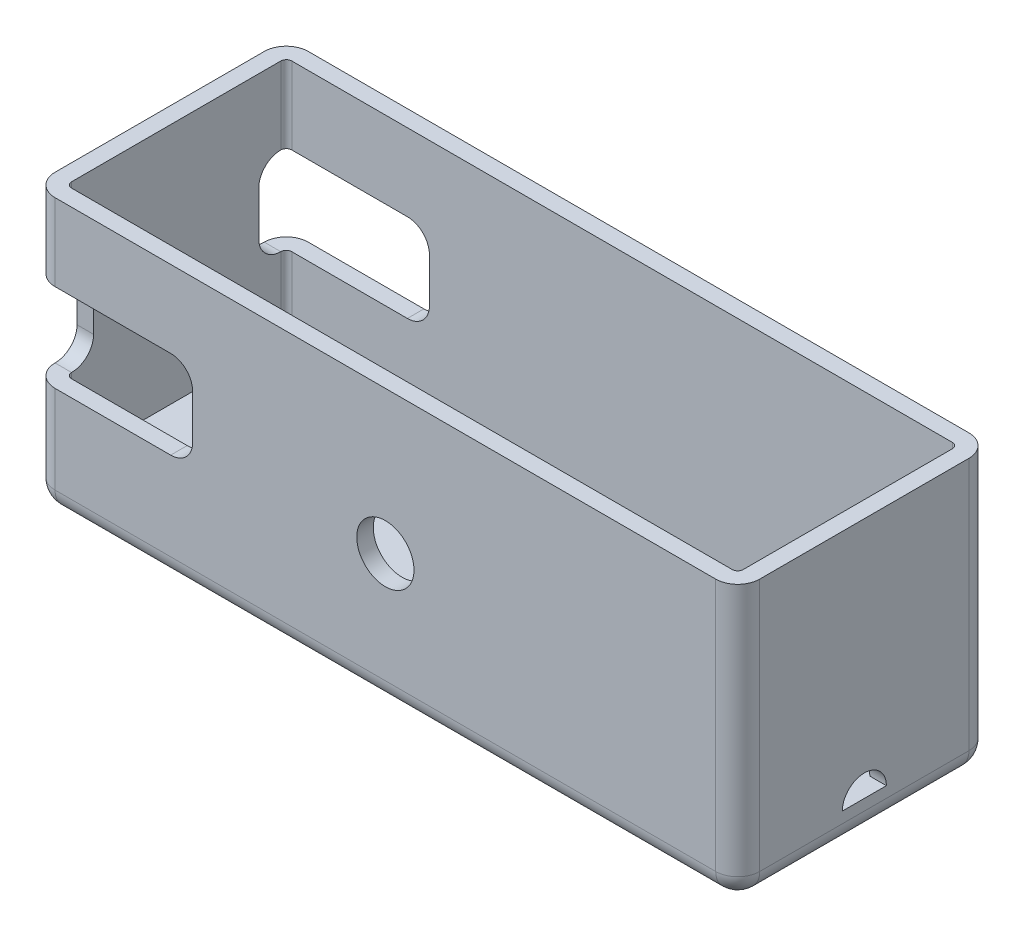
SolidWorks part; units mm, degrees
ref_plane "Front Plane" through (0, 0, 0) normal (0, 0, 1) x (1, 0, 0)
ref_plane "Top Plane" through (0, 0, 0) normal (0, 1, 0) x (1, 0, 0)
ref_plane "Right Plane" through (0, 0, 0) normal (1, 0, 0) x (0, 0, -1)
sketch "Sketch1" plane through (0, 0, 0) normal (0, 1, 0) x (1, 0, 0)
  line L1 (32, -11.5) -> (-32, -11.5)
  line L2 (32, -11.5) -> (32, 11.5)
  line L3 (32, 11.5) -> (-32, 11.5)
  line L4 (-32, -11.5) -> (-32, 11.5)
  line L5 (0, 11.5) -> (0, -11.5) construction
  line L6 (32, 0) -> (-32, 0) construction
  line L7 (30.5, -10) -> (-30.5, -10)
  line L8 (30.5, -10) -> (30.5, 10)
  line L9 (30.5, 10) -> (-30.5, 10)
  line L10 (-30.5, -10) -> (-30.5, 10)
  line L11 (0, 10) -> (0, -10) construction
  line L12 (30.5, 0) -> (-30.5, 0) construction
  point P0 (0, 0)
  point P4 (0, 0)
  dimension "D1" = 20
  dimension "D2" = 61
  dimension "D3" = 1.5
  dimension "D4" = 1.5
extrude "Boss-Extrude1" add sketch "Sketch1" against normal blind 3 contours L10 L7 L8 L9 | L4 L1 L2 L3 L7 L10 L9 L8 region at (0, 0, 10.8199) region at (0, 0, 0)
extrude "Boss-Extrude2" add sketch "Sketch1<3>" along normal blind 22
sketch "Sketch1<3>" plane through (0, 0, 0) normal (0, 1, 0) x (1, 0, 0) same geometry as "Sketch1"
fillet "Fillet1" radius 2 8 edges at (0, -3, 11.5) (32, -3, 0) (0, -3, -11.5) (-32, -3, 0) (-32, 9.5, -11.5) (-32, 9.5, 11.5) (32, 9.5, 11.5) (32, 9.5, -11.5)
fillet "Fillet2" radius 0.5 4 edges at (30.5, 11, -10) (-30.5, 11, -10) (30.5, 11, 10) (-30.5, 11, 10)
sketch "Sketch2" plane through (32, 0, 0) normal (1, 0, 0) x (0, 0, -1)
  line L1 (-2, 0) -> (2, 0)
  line L2 (-9.5, 0) -> (9.5, 0) construction
  line L3 (-9.5, 0) -> (9.5, 0) construction
  arc A0 (-2, 0) -> (2, 0) centre (0, 0) cw
  dimension "D1" = 2
extrude "Cut-Extrude1" cut sketch "Sketch2" against normal up to surface (1.5 mm away) contours A0 L1 region at (32, 0.8488, 0) up to face at (30.5, 11, 0)
sketch "Sketch3" plane through (0, 0, 0) normal (0, 1, 0) x (1, 0, 0)
  line L0 (-32, 0) -> (32, 0) construction
  line L1 (-32, 9.5) -> (-32, -9.5) construction
  line L2 (32, -9.5) -> (32, 9.5) construction
  line L3 (30.5, 2) -> (30.5, 9.5) construction
  line L4 (30.5, -9.5) -> (30.5, 9.5) construction
  circle A0 centre (19.4, 0) radius 1.1
  circle A1 centre (-4.6, 0) radius 1.1
  dimension "D1" = 2.2
  dimension "D2" = 2.2
  dimension "D3" = 11.1
  dimension "D4" = 35.1
extrude "Cut-Extrude2" cut sketch "Sketch3" against normal through all
sketch "Sketch4" plane through (0, 0, 11.5) normal (0, 0, 1) x (1, 0, 0)
  line L0 (-30, 0) -> (30, 0) construction
  line L1 (-17.5, 7) -> (-28, 7)
  line L2 (-17.5, 7) -> (-17.5, 15)
  line L3 (-17.5, 15) -> (-28, 15)
  line L4 (-28, 7) -> (-28, 15)
  line L5 (-22.75, 15) -> (-22.75, 7) construction
  line L6 (-17.5, 11) -> (-28, 11) construction
  line L7 (30.5, 0) -> (30.5, 22) construction
  line L8 (-30, 22) -> (-30, -1) construction
  point P0 (-22.75, 11)
  dimension "D1" = 11
  dimension "D2" = 8
  dimension "D3" = 48
  dimension "D4" = 2
extrude "Cut-Extrude3" cut sketch "Sketch4" against normal through all
sketch "Sketch5" plane through (-32, 0, 0) normal (-1, 0, 0) x (0, 0, 1)
  line L0 (-11.5, 7) -> (-10, 7) construction
  line L1 (-11.5, 15) -> (-7.5, 15)
  line L2 (-11.5, 15) -> (-11.5, 7)
  line L3 (-11.5, 7) -> (-7.5, 7)
  line L4 (-7.5, 15) -> (-7.5, 7)
  line L5 (-9.5, 7) -> (-9.5, 15) construction
  line L6 (-11.5, 11) -> (-7.5, 11) construction
  line L7 (-11.5, 15) -> (-10, 15) construction
  line L8 (-11.5, -1) -> (-11.5, 22) construction
  line L9 (0, -1.65) -> (0, 1.65) construction
  line L10 (11.5, 11) -> (7.5, 11) construction
  line L11 (9.5, 7) -> (9.5, 15) construction
  line L12 (7.5, 15) -> (7.5, 7)
  line L13 (11.5, 7) -> (7.5, 7)
  line L14 (11.5, 15) -> (11.5, 7)
  line L15 (11.5, 15) -> (7.5, 15)
  point P0 (-9.5, 11)
  point P23 (9.5, 11)
  dimension "D1" = 15
extrude "Cut-Extrude4" cut sketch "Sketch5" against normal up to surface (14.5 mm away) up to face at (-17.5, 11, -10.75)
fillet "Fillet3" radius 2 8 edges at (-17.5, 7, -10.75) (-17.5, 15, -10.75) (-17.5, 7, 10.75) (-17.5, 15, 10.75) (-31.25, 7, -7.5) (-31.25, 15, -7.5) (-31.25, 15, 7.5) (-31.25, 7, 7.5)
sketch "Sketch6" plane through (0, -3, 0) normal (0, -1, 0) x (1, 0, 0)
  circle A0 centre (-4.6, 0) radius 3
  circle A1 centre (19.4, 0) radius 3
  dimension "D2" = 6
extrude "Cut-Extrude5" cut sketch "Sketch6" against normal blind 1.5
sketch "Sketch7" plane through (0, 0, 0) normal (1, 0, 0) x (0, 0, -1)
  line L0 (-11.5, -3) -> (-9.5, -3)
  line L5 (-11.5, -1) -> (-11.5, 22) construction
  line L7 (-11.5, 9.5) -> (11.5, 9.5) construction
  line L8 (11.5, 22) -> (11.5, -1) construction
  line L9 (11.5, 22) -> (11.5, -3) construction
  line L10 (9.5, -3) -> (-9.5, -3) construction
  line L11 (-17.0981, 1.5) -> (-11.5, 11.1962)
  line L12 (-11.5, -3) -> (-14.5, -3)
  line L13 (-11.5, 3) -> (-17.5, 3)
  line L14 (-11.5, -3) -> (-11.5, 3)
  line L15 (-11.5, 11.1962) -> (-11.5, 3)
  line L16 (-17.5, 0) -> (-17.5, 3)
  arc A2 (-9.5, -3) -> (-11.5, -1) centre (-9.5, -1) cw
  arc A3 (-17.5, 0) -> (-14.5, 3) centre (-14.5, 0) cw
  arc A4 (-17.5, 0) -> (-14.5, -3) centre (-14.5, 0) ccw
  circle A5 centre (-14.5, 0) radius 2
  dimension "D1" = 6
  dimension "D5" = 30
  dimension "D3" = 4
  dimension "D4" = 1
  dimension "D2" = 6
extrude "Boss-Extrude3" [suppressed] add sketch "Sketch7" along normal blind 5 from offset 5.2 contours L15 L11 L13 | A3 A4 L12 L14 L13 A5 | L0 A2 L14 | L11 A3 L13
mirror "Mirror1" [suppressed] about plane through (0, 0, 0) normal (1, 0, 0)
sketch "Sketch9" plane through (0, -3, 0) normal (0, -1, 0) x (1, 0, 0)
  line L0 (30, -11.5) -> (-30, -11.5) construction
  line L1 (-16.5, -11.5) -> (16.5, -11.5)
  line L2 (-16.5, -11.5) -> (-16.5, -12)
  line L3 (-14, -14.5) -> (14, -14.5)
  line L4 (16.5, -11.5) -> (16.5, -12)
  line L6 (-15, -11.5) -> (15, -11.5)
  line L7 (-15, -11.5) -> (-15, -12)
  line L8 (-14, -13) -> (14, -13)
  line L9 (15, -11.5) -> (15, -12)
  arc A0 (-14, -13) -> (-15, -12) centre (-14, -12) cw
  arc A1 (14, -13) -> (15, -12) centre (14, -12) ccw
  arc A2 (14, -14.5) -> (16.5, -12) centre (14, -12) ccw
  arc A3 (-14, -14.5) -> (-16.5, -12) centre (-14, -12) cw
  point P10 (0, -13)
  point P11 (0, -14.5)
  dimension "D5" = 1
  dimension "D1" = 1.5
  dimension "D2" = 1.5
  dimension "D3" = 1.5
  dimension "D4" = 30
extrude "Boss-Extrude4" add sketch "Sketch9" against normal blind 3 from vertex contours A3 L3 A2 L4 L1 L9 A1 L8 A0 L7 L2 region at (0, -3, -13.6016) starting at point (30, -1, -11.5)
fillet "Fillet4" radius 0.5 20 edges at (-15, 2, -11.75) (-14.7071, 2, -12.7071) (15, 2, -11.75) (14.7071, 2, -12.7071) (-16.5, -1, -11.75) (-15.7678, -1, -13.7678) (16.5, -1, -11.75) (15.7678, -1, -13.7678) (-16.5, 2, -11.75) (-15.7678, 2, -13.7678) (16.5, 2, -11.75) (15.7678, 2, -13.7678) (-15, -1, -11.75) (-14.7071, -1, -12.7071) (15, -1, -11.75) (14.7071, -1, -12.7071) (0, 2, -13) (0, -1, -14.5) (0, 2, -14.5) (0, -1, -13)
fillet "Fillet5" radius 0.5 16 edges at (16.3536, 1.8536, -11.5) (15.75, 2, -11.5) (15.1464, 1.8536, -11.5) (15, 0.5, -11.5) (15.1464, -0.8536, -11.5) (-15.75, -1, -11.5) (15.75, -1, -11.5) (16.3536, -0.8536, -11.5) (-15.1464, 1.8536, -11.5) (-15.75, 2, -11.5) (-16.3536, 1.8536, -11.5) (-16.5, 0.5, -11.5) (-16.3536, -0.8536, -11.5) (-15.1464, -0.8536, -11.5) (16.5, 0.5, -11.5) (-15, 0.5, -11.5)
sketch "Sketch10" plane through (0, 0, 11.5) normal (0, 0, 1) x (1, 0, 0)
  line L0 (-30, -1) -> (30, -1) construction
  circle A0 centre (0, 9) radius 2.6
  dimension "D1" = 5.2
  dimension "D2" = 10
extrude "Cut-Extrude6" cut sketch "Sketch10" against normal up to surface (1.5 mm away) and the other way through all contours A0 up to face at (-13.3172, 11, 10)
